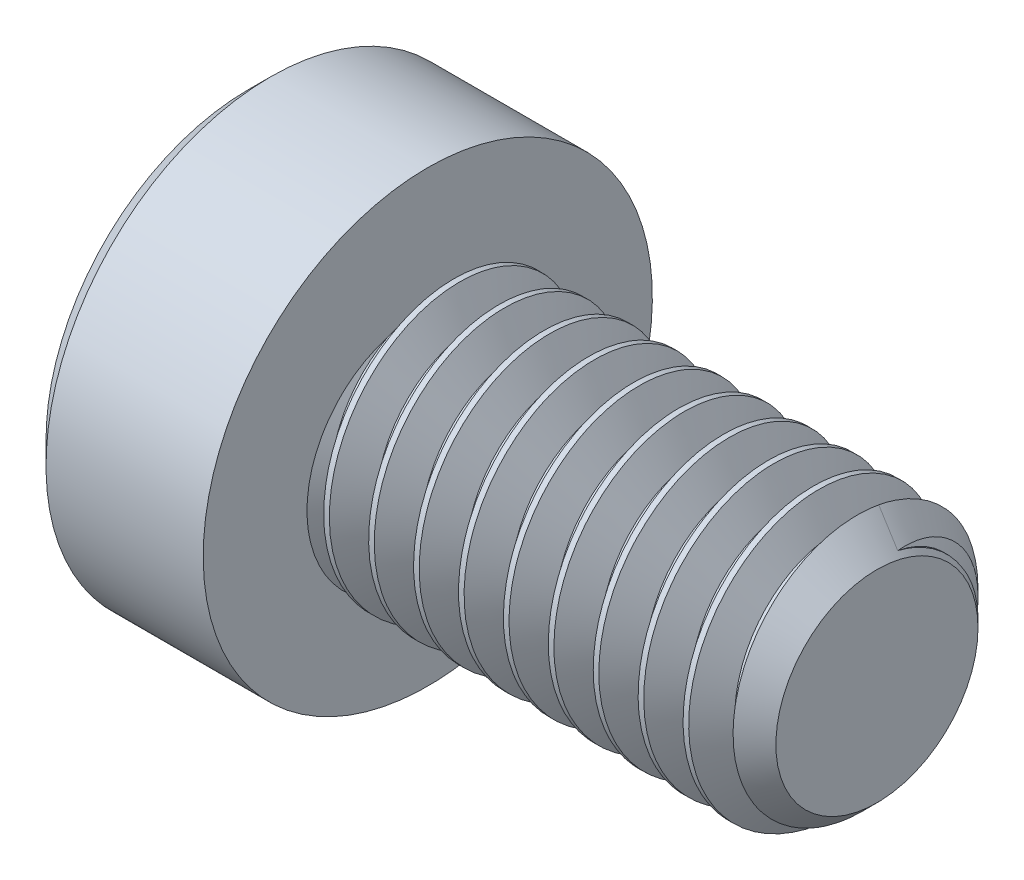
SolidWorks part; units mm, degrees
ref_plane "Front Plane" through (0, 0, 0) normal (0, 0, 1) x (1, 0, 0)
ref_plane "Top Plane" through (0, 0, 0) normal (0, 1, 0) x (1, 0, 0)
ref_plane "Right Plane" through (0, 0, 0) normal (1, 0, 0) x (0, 0, -1)
sketch "Sketch1" plane through (0, 0, 0) normal (0, 0, 1) x (1, 0, 0)
  line L0 (5, 0) -> (-5, 0) construction
  line L1 (5, 3) -> (5, -3) construction
  line L2 (-5, 5) -> (-5, -5) construction
  line L3 (-5, 5) -> (-8.5, 5) construction
  line L4 (-8.5, 5) -> (-9, 4.5) construction
  line L5 (-9, 4.5) -> (-9, -4.5) construction
  line L6 (-9, -4.5) -> (-8.5, -5) construction
  line L7 (-8.5, -5) -> (-5, -5) construction
  point P7 (-5.88, 0)
  point P12 (1, -3)
  dimension "D1" = 45
  dimension "Dec." = 6
  dimension "Length" = 10
  dimension "Head Dia" = 10
  dimension "Head Height" = 4
  dimension "Hex Depth" = 3.12
  dimension "Chamfer" = 0.5
  dimension "D2" = 4
ref_plane "Plane1" through (5, 0, 0) normal (1, 0, 0) x (0, 0, -1)
ref_plane "Plane2" through (-9, 0, 0) normal (1, 0, 0) x (0, 0, -1)
sketch "Sketch2" plane through (5, 0, 0) normal (1, 0, 0) x (0, 0, -1)
  circle A0 centre (0, 0) radius 3
extrude "Boss-Extrude1" add sketch "Sketch2" against normal up to vertex (10 mm away) up to point (-5, 0, 0)
sketch "Sketch3" plane through (5, 0, 0) normal (1, 0, 0) x (0, 0, -1)
  circle A0 centre (0, 0) radius 3 construction
  circle A1 centre (0, 0) radius 3
curve "Helix/Spiral1" pitch 1 height 11 radius 3 centre (5, 0, 0) axis (-1, 0, 0) start towards (0, 1, 0) parameters "Pitch"=1
chamfer "Chamfer1" distance 0.75 angle 45 1 edges at (5, 0, -3)
sketch "Sketch5" plane through (0, 0, 0) normal (0, 0, 1) x (1, 0, 0)
  line L0 (4.5625, 3) -> (5.4375, 3)
  line L1 (5.4375, 3) -> (5.0625, 2.3505)
  line L2 (5.0625, 2.3505) -> (4.9375, 2.3505)
  line L3 (4.9375, 2.3505) -> (4.5625, 3)
  line L4 (5, 2.3505) -> (5, 3) construction
  line L5 (4.75, 2.6752) -> (5.25, 2.6752) construction
  dimension "D1" = 60
  dimension "D2" = 0.5
  dimension "D3" = 0.125
sweep "Cut-Sweep1" cut profiles "Sketch5" path "Helix/Spiral1" align with end faces yes
sketch "Sketch4" plane through (-9, 0, 0) normal (1, 0, 0) x (0, 0, -1)
  line L0 (-5, 0.7937) -> (5, 0.7937) construction
  line L1 (0, 2.3094) -> (-2, 1.1547)
  line L2 (-2, 1.1547) -> (-2, -1.1547)
  line L3 (-2, -1.1547) -> (0, -2.3094)
  line L4 (0, -2.3094) -> (2, -1.1547)
  line L5 (2, -1.1547) -> (2, 1.1547)
  line L6 (2, 1.1547) -> (0, 2.3094)
  line L7 (0, 0) -> (0, 0.7937) construction
  circle A0 centre (0, 0) radius 2 construction
  dimension "Hex Size" = 4
  dimension "D1" = 10
  dimension "D2" = 0.7937
sketch "Sketch6" plane through (0, 0, 0) normal (0, 0, 1) x (1, 0, 0)
  line L0 (-8.5, 5) -> (-9, 4.5) construction
  line L1 (-5, 5) -> (-8.5, 5) construction
  line L2 (-5, 5) -> (-5, -5) construction
  line L3 (-9, 4.5) -> (-9, -4.5) construction
  line L4 (-8.5, 5) -> (-9, 4.5)
  line L5 (-5, 5) -> (-8.5, 5)
  line L6 (-5, 5) -> (-5, 0)
  line L7 (-9, 4.5) -> (-9, 0)
  line L8 (-5, 0) -> (-9, 0) construction
  line L9 (-5, 0) -> (-9, 0)
revolve "Revolve1" add sketch "Sketch6" angle 360 about L8
extrude "Cut-Extrude1" cut sketch "Sketch4" along normal up to vertex (3.12 mm away) up to point (-5.88, 0, 0)
sketch "Sketch8" plane through (-9, 0, 0) normal (-1, 0, 0) x (0, 0, 1)
  circle A1 centre (0, 0) radius 2.3094
extrude "Cut-Extrude2" cut sketch "Sketch8" against normal through all draft 45
equation "\"D3@Helix/Spiral1\" = \"Length@Sketch1\"+\"Pitch@Helix/Spiral1\""
equation "\"D3@Sketch5\" = \"Pitch@Helix/Spiral1\"*.125"
equation "\"D2@Sketch5\" = \"Pitch@Helix/Spiral1\"*.50"
equation "\"D1@Chamfer1\" = \"Pitch@Helix/Spiral1\"*.75"
equation "\"D2@Sketch1\" = \"Pitch@Helix/Spiral1\"*4"
equation "\"D1@Sketch4\" = \"Head Dia@Sketch1\""
equation "\"Chamfer@Sketch1\" = \"Head Height@Sketch1\"/8"
